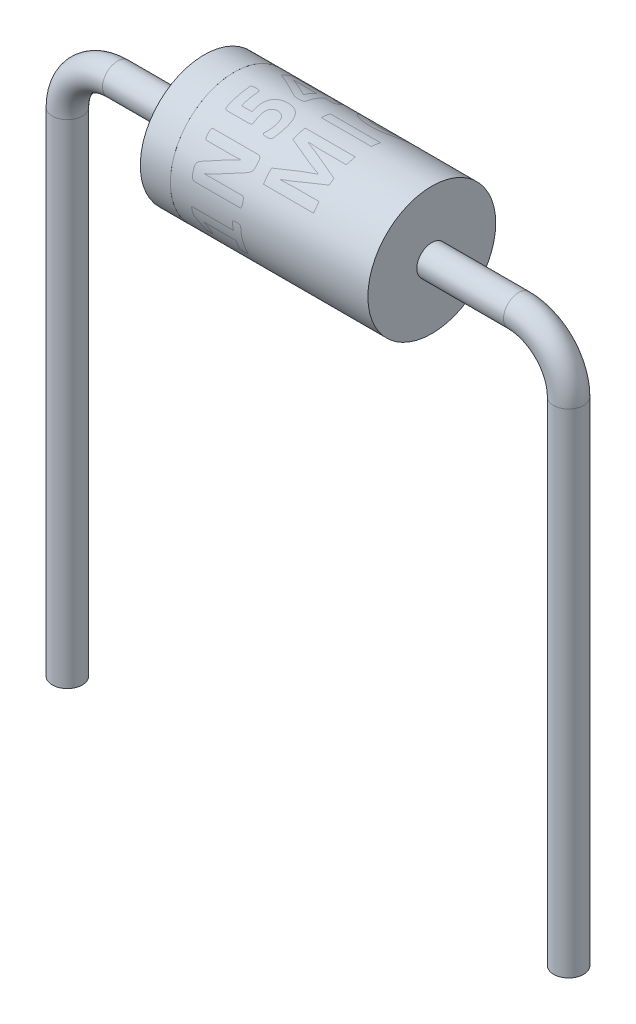
SolidWorks part; units mm, degrees
other "Wire"
other "Cathode Silver Band"
other "Diode"
ref_plane "Front Plane" through (0, 0, 0) normal (0, 0, 1) x (1, 0, 0)
ref_plane "Top Plane" through (0, 0, 0) normal (0, 1, 0) x (1, 0, 0)
ref_plane "Right Plane" through (0, 0, 0) normal (1, 0, 0) x (0, 0, -1)
sketch "Sketch1" plane through (0, 0, 0) normal (1, 0, 0) x (0, 0, -1)
  circle A0 centre (0, 0) radius 2.55
  circle A1 centre (0, 0) radius 0.6
  dimension "D1" = 5.1
  dimension "D2" = 1.2
extrude "Boss-Extrude1" add sketch "Sketch1" along normal mid plane 9.08
sketch "Sketch2" plane through (-4.54, 0, 0) normal (-1, 0, 0) x (0, 0, 1)
  circle A1 centre (0, 0) radius 2.55 construction
  circle A2 centre (0, 0) radius 2.54
  circle A3 centre (0, 0) radius 2.54
  circle A4 centre (0, 0) radius 2.55
  dimension "D1" = 0.01
extrude "Cut-Extrude1" cut sketch "Sketch2" against normal blind 1.2
sketch "Sketch3" plane through (-3.34, 0, 0) normal (-1, 0, 0) x (0, 0, 1)
  circle A0 centre (0, 0) radius 2.54 construction
  circle A1 centre (0, 0) radius 2.54
  circle A2 centre (0, 0) radius 2.55 construction
  circle A3 centre (0, 0) radius 2.55
extrude "Boss-Extrude2" add sketch "Sketch3" along normal up to surface (1.2 mm away) separate body up to face at (-4.54, 0, -0.6)
ref_plane "Plane1" through (0, 5, 0) normal (0, 1, 0) x (1, 0, 0)
sketch "Sketch4" plane through (0, 5, 0) normal (0, 1, 0) x (1, 0, 0)
  line L0 (-0.54, 7.5) -> (-0.54, -7.5) construction
  line L1 (-0.54, 0) -> (-4.54, 0) construction
  line L2 (-4.54, 2.55) -> (-4.54, -2.55) construction
  line L4 (-0.54, 0) -> (1.96, 0) construction
  line L5 (1.96, 7.5) -> (1.96, -7.5) construction
  text T0 "1N5406" font "Calibri" height 2
  text T1 "MIC" font "Corbel" height 2
  dimension "D1" = 4
  dimension "D2" = 15
  dimension "D3" = 2.5
wrap "Wrap1" sketch "Sketch4" wrap type scribe source sketch "Sketch4" face at (4.54, 0, -2.55)
sketch "Sketch5" plane through (0, 0, 0) normal (0, 0, 1) x (1, 0, 0)
  line L0 (0, 0) -> (-8, 0)
  line L1 (-10, -2) -> (-10, -21.6584)
  line L2 (0, 0) -> (8, 0)
  line L3 (10, -2) -> (10, -21.6584)
  arc A0 (-8, 0) -> (-10, -2) centre (-8, -2) ccw
  arc A1 (8, 0) -> (10, -2) centre (8, -2) cw
  dimension "D2" = 2
  dimension "D3" = 61.6
  dimension "D1" = 20
sketch "Sketch6" plane through (0, 0, 0) normal (1, 0, 0) x (0, 0, -1)
  circle A0 centre (0, 0) radius 0.6
  dimension "D1" = 1.2
sweep "Sweep1" add profiles "Sketch6" path "Sketch5"
